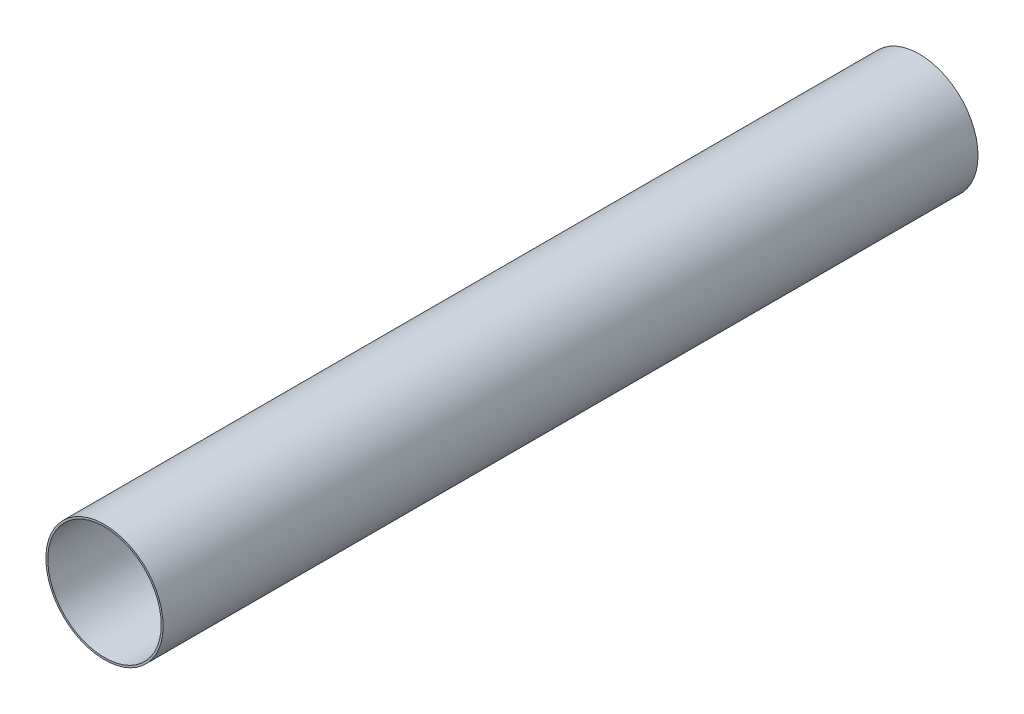
SolidWorks part; units mm, degrees
material "A-Glass Fiber"
ref_plane "Front Plane" through (0, 0, 0) normal (0, 0, 1) x (1, 0, 0)
ref_plane "Top Plane" through (0, 0, 0) normal (0, 1, 0) x (1, 0, 0)
ref_plane "Right Plane" through (0, 0, 0) normal (1, 0, 0) x (0, 0, -1)
sketch "Sketch2" plane through (0, 0, 0) normal (0, 0, 1) x (1, 0, 0)
  circle A0 centre (0, 0) radius 49.5
  circle A1 centre (0, 0) radius 51.15
  dimension "D1" = 99
  dimension "D2" = 102.3
extrude "Boss-Extrude1" add sketch "Sketch2" along normal blind 355.6 and the other way blind 355.6
